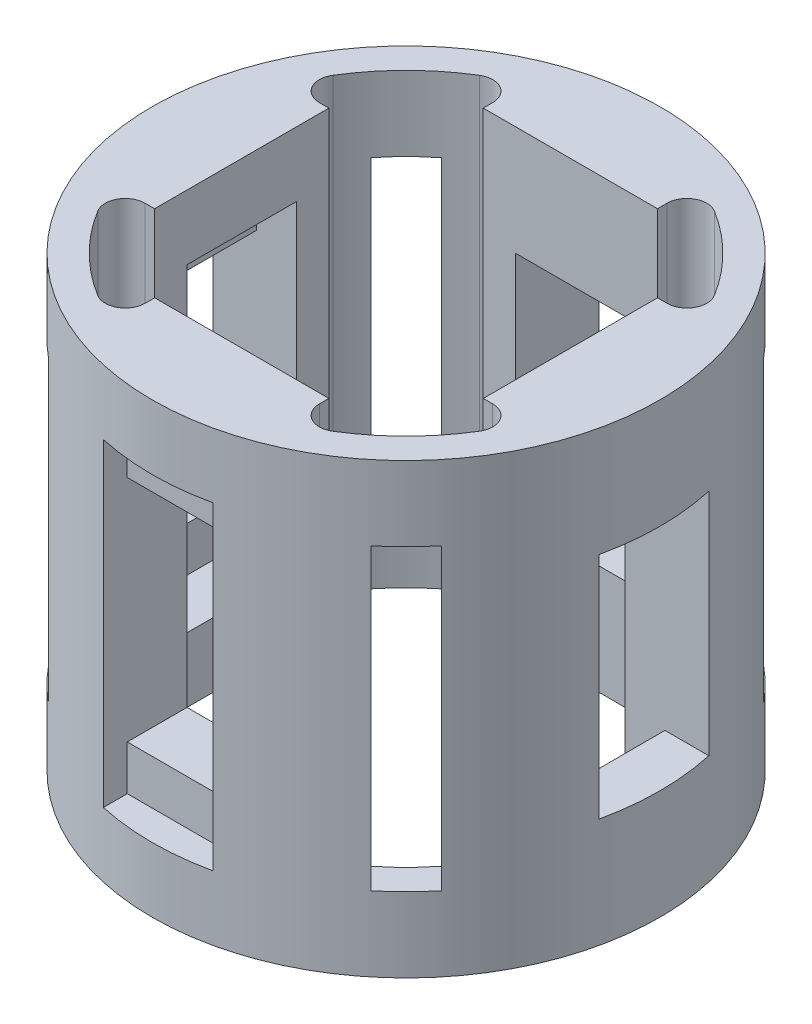
SolidWorks part; units mm, degrees
ref_plane "Front Plane" through (0, 0, 0) normal (0, 0, 1) x (1, 0, 0)
ref_plane "Top Plane" through (0, 0, 0) normal (0, 1, 0) x (1, 0, 0)
ref_plane "Right Plane" through (0, 0, 0) normal (1, 0, 0) x (0, 0, -1)
sketch "Sketch1" plane through (0, 0, 0) normal (0, 1, 0) x (1, 0, 0)
  line L5 (-8.75, -19.5) -> (8.75, -19.5)
  line L6 (-8.75, -19.5) -> (-8.75, -25.5)
  line L7 (-8.75, -25.5) -> (8.75, -25.5)
  line L8 (8.75, -19.5) -> (8.75, -25.5)
  line L9 (-8.75, -19.5) -> (8.75, -25.5) construction
  line L10 (-8.75, -25.5) -> (8.75, -19.5) construction
  line L11 (-25.5, 8.75) -> (-19.5, 8.75)
  line L12 (-25.5, 8.75) -> (-25.5, -8.75)
  line L13 (-25.5, -8.75) -> (-19.5, -8.75)
  line L14 (-19.5, 8.75) -> (-19.5, -8.75)
  line L15 (-25.5, 8.75) -> (-19.5, -8.75) construction
  line L16 (-25.5, -8.75) -> (-19.5, 8.75) construction
  line L17 (-8.75, 25.5) -> (8.75, 25.5)
  line L18 (-8.75, 25.5) -> (-8.75, 19.5)
  line L19 (-8.75, 19.5) -> (8.75, 19.5)
  line L20 (8.75, 25.5) -> (8.75, 19.5)
  line L21 (-8.75, 25.5) -> (8.75, 19.5) construction
  line L22 (-8.75, 19.5) -> (8.75, 25.5) construction
  line L23 (19.5, 8.75) -> (25.5, 8.75)
  line L24 (19.5, 8.75) -> (19.5, -8.75)
  line L25 (19.5, -8.75) -> (25.5, -8.75)
  line L26 (25.5, 8.75) -> (25.5, -8.75)
  line L27 (19.5, 8.75) -> (25.5, -8.75) construction
  line L28 (19.5, -8.75) -> (25.5, 8.75) construction
  line L29 (-8.75, -19.5) -> (8.75, -19.5)
  line L30 (-8.75, -19.5) -> (-8.75, -16.5)
  line L31 (-8.75, -16.5) -> (8.75, -16.5)
  line L32 (8.75, -19.5) -> (8.75, -16.5)
  line L33 (-19.5, 8.75) -> (-16.5, 8.75)
  line L34 (-19.5, 8.75) -> (-19.5, -8.75)
  line L35 (-19.5, -8.75) -> (-16.5, -8.75)
  line L36 (-16.5, 8.75) -> (-16.5, -8.75)
  line L37 (19.5, -8.75) -> (16.5, -8.75)
  line L38 (19.5, -8.75) -> (19.5, 8.75)
  line L39 (19.5, 8.75) -> (16.5, 8.75)
  line L40 (16.5, -8.75) -> (16.5, 8.75)
  line L41 (-8.75, 19.5) -> (8.75, 19.5)
  line L42 (-8.75, 19.5) -> (-8.75, 16.5)
  line L43 (-8.75, 16.5) -> (8.75, 16.5)
  line L44 (8.75, 19.5) -> (8.75, 16.5)
  circle A0 centre (0, 0) radius 25.5
  circle A1 centre (0, 0) radius 22.5
  point P4 (0, -22.5)
  point P9 (-22.5, 0)
  point P14 (0, 22.5)
  point P19 (22.5, 0)
  dimension "D1" = 51
  dimension "D2" = 45
  dimension "D3" = 6
  dimension "D4" = 17.5
  dimension "D5" = 6
  dimension "D6" = 17.5
  dimension "D7" = 6
  dimension "D8" = 6
  dimension "D9" = 17.5
  dimension "D10" = 17.5
  dimension "D11" = 3
  dimension "D12" = 3
  dimension "D13" = 3
  dimension "D14" = 3
extrude "Boss-Extrude1" add sketch "Sketch1" along normal blind 45 contours A1 L13 A0 L6 | A1 L11 A0 L13 | A1 L18 A0 L11 | A1 L20 A0 L18 | L20 A1 L18 L19 | L44 L19 L42 L43 | L36 L33 L14 L35 | L11 A1 L13 L14 | A1 L6 A0 L8 | L6 A1 L8 L5 | L5 L32 L31 L30 | A1 L8 A0 L25 | L40 L37 L24 L39 | L25 A1 L23 L24 | A1 L25 A0 L23 | A1 L23 A0 L20 region at (0, 0, 18) region at (0, 0, 20.7666) region at (0, 0, 23.4443) region at (-16.5332, 0, 16.5332) region at (16.5332, 0, 16.5332) region at (-20.7666, 0, 0) region at (-23.4443, 0, 0) region at (23.4443, 0, 0) region at (20.7666, 0, 0) region at (-18, 0, 0) region at (-16.5332, 0, -16.5332) region at (18, 0, 0) region at (0, 0, -20.7666) region at (0, 0, -23.4443) region at (16.5332, 0, -16.5332) region at (0, 0, -18)
fillet "Fillet1" radius 2 8 edges at (20.7289, 22.5, -8.75) (20.7289, 22.5, 8.75) (8.75, 22.5, 20.7289) (-8.75, 22.5, -20.7289) (8.75, 22.5, -20.7289) (-8.75, 22.5, 20.7289) (-20.7289, 22.5, 8.75) (-20.7289, 22.5, -8.75)
ref_plane "Plane1" through (0, 0, 0) normal (0.7071, 0, -0.7071) x (-0.7071, 0, -0.7071)
sketch "Sketch2" plane through (0, 0, 0) normal (0.7071, 0, -0.7071) x (-0.7071, 0, -0.7071)
  line L0 (0, 0) -> (0, 22.5)
  line L2 (2.5, 7.5) -> (-2.5, 7.5)
  line L3 (2.5, 7.5) -> (2.5, 37.5)
  line L4 (2.5, 37.5) -> (-2.5, 37.5)
  line L5 (-2.5, 7.5) -> (-2.5, 37.5)
  line L6 (2.5, 7.5) -> (-2.5, 37.5) construction
  line L7 (2.5, 37.5) -> (-2.5, 7.5) construction
  dimension "D1" = 22.5
  dimension "D2" = 30
  dimension "D3" = 5
extrude "Cut-Extrude1" cut sketch "Sketch2" against normal through all and the other way through all contours L5 L2 L3 L4 region at (-0.8839, 7.8041, -0.8839)
ref_plane "Plane2" through (0, 0, 0) normal (0.7071, 0, 0.7071) x (0.7071, 0, -0.7071)
sketch "Sketch3" plane through (0, 0, 0) normal (0.7071, 0, 0.7071) x (0.7071, 0, -0.7071)
  line L0 (0, 0) -> (0, 22.5)
  line L2 (2.5, 37.5) -> (-2.5, 37.5)
  line L3 (2.5, 37.5) -> (2.5, 7.5)
  line L4 (2.5, 7.5) -> (-2.5, 7.5)
  line L5 (-2.5, 37.5) -> (-2.5, 7.5)
  line L6 (2.5, 37.5) -> (-2.5, 7.5) construction
  line L7 (2.5, 7.5) -> (-2.5, 37.5) construction
  dimension "D1" = 22.5
  dimension "D2" = 5
  dimension "D3" = 30
extrude "Cut-Extrude2" cut sketch "Sketch3" against normal through all and the other way through all contours L2 L5 L4 L3 region at (1.5527, 22.5, -1.5527)
sketch "Sketch4" plane through (0, 0, 0) normal (0, 0, 1) x (1, 0, 0)
  line L0 (0, 0) -> (0, 22.5)
  line L2 (-5.5, 34) -> (5.5, 34)
  line L3 (-5.5, 34) -> (-5.5, 11)
  line L4 (-5.5, 11) -> (5.5, 11)
  line L5 (5.5, 34) -> (5.5, 11)
  line L6 (-5.5, 34) -> (5.5, 11) construction
  line L7 (-5.5, 11) -> (5.5, 34) construction
  dimension "D1" = 22.5
  dimension "D2" = 11
  dimension "D3" = 23
extrude "Cut-Extrude3" cut sketch "Sketch4" against normal through all and the other way through all contours L5 L2 L3 L4 region at (0, 33.745, 0)
sketch "Sketch5" plane through (0, 0, 0) normal (1, 0, 0) x (0, 0, -1)
  line L0 (0, 0) -> (0, 22.5)
  line L2 (5.5, 11) -> (-5.5, 11)
  line L3 (5.5, 11) -> (5.5, 34)
  line L4 (5.5, 34) -> (-5.5, 34)
  line L5 (-5.5, 11) -> (-5.5, 34)
  line L6 (5.5, 11) -> (-5.5, 34) construction
  line L7 (5.5, 34) -> (-5.5, 11) construction
  dimension "D1" = 22.5
  dimension "D2" = 23
  dimension "D3" = 11
extrude "Cut-Extrude4" cut sketch "Sketch5" against normal through all and the other way through all contours L5 L2 L3 L4 region at (0, 11.255, -2.75)
sketch "Sketch6" plane through (16.5, 0, 0) normal (-1, 0, 0) x (0, 0, 1)
  line L1 (-5.5, 34) -> (5.5, 34)
  line L2 (-5.5, 34) -> (-5.5, 38.5)
  line L3 (-5.5, 38.5) -> (5.5, 38.5)
  line L4 (5.5, 34) -> (5.5, 38.5)
  line L5 (-5.5, 11) -> (5.5, 11)
  line L6 (-5.5, 11) -> (-5.5, 6.5)
  line L7 (-5.5, 6.5) -> (5.5, 6.5)
  line L8 (5.5, 11) -> (5.5, 6.5)
  dimension "D1" = 4.5
  dimension "D2" = 4.5
  dimension "D3" = 11
  dimension "D4" = 11
sketch "Sketch7" plane through (-16.5, 0, 0) normal (1, 0, 0) x (0, 0, -1)
  line L1 (5.5, 34) -> (-5.5, 34)
  line L2 (5.5, 34) -> (5.5, 38.5)
  line L3 (5.5, 38.5) -> (-5.5, 38.5)
  line L4 (-5.5, 34) -> (-5.5, 38.5)
  line L5 (5.5, 11) -> (-5.5, 11)
  line L6 (5.5, 11) -> (5.5, 6.5)
  line L7 (5.5, 6.5) -> (-5.5, 6.5)
  line L8 (-5.5, 11) -> (-5.5, 6.5)
  dimension "D1" = 4.5
  dimension "D2" = 4.5
  dimension "D3" = 11
  dimension "D4" = 11
sketch "Sketch10" plane through (-16.5, 0, 0) normal (1, 0, 0) x (0, 0, -1)
  line L1 (-5.5, 11) -> (5.5, 11)
  line L2 (-5.5, 11) -> (-5.5, 6.5)
  line L3 (-5.5, 6.5) -> (5.5, 6.5)
  line L4 (5.5, 11) -> (5.5, 6.5)
  dimension "D1" = 4.5
  dimension "D2" = 11
extrude "Cut-Extrude11" cut sketch "Sketch10" against normal blind 5
extrude "Cut-Extrude12" cut sketch "Sketch6" against normal blind 4
extrude "Cut-Extrude13" cut sketch "Sketch7" against normal blind 4
ref_plane "Plane3" through (0, 0, 25.5) normal (0, 0, 1) x (1, 0, 0)
ref_plane "Plane4" through (0, 0, -25.5) normal (0, 0, 1) x (1, 0, 0)
sketch "Sketch11" plane through (0, 0, 25.5) normal (0, 0, 1) x (1, 0, 0)
  line L1 (-5.5, 11) -> (5.5, 11)
  line L2 (-5.5, 11) -> (-5.5, 6.5)
  line L3 (-5.5, 6.5) -> (5.5, 6.5)
  line L4 (5.5, 11) -> (5.5, 6.5)
  line L5 (-5.5, 34) -> (5.5, 34)
  line L6 (-5.5, 34) -> (-5.5, 38.5)
  line L7 (-5.5, 38.5) -> (5.5, 38.5)
  line L8 (5.5, 34) -> (5.5, 38.5)
  dimension "D1" = 11
  dimension "D2" = 11
  dimension "D3" = 4.5
  dimension "D4" = 4.5
extrude "Cut-Extrude14" cut sketch "Sketch11" against normal blind 3
sketch "Sketch13" plane through (0, 0, -25.5) normal (0, 0, 1) x (1, 0, 0)
  line L1 (-5.5, 34) -> (5.5, 34)
  line L2 (-5.5, 34) -> (-5.5, 38.5)
  line L3 (-5.5, 38.5) -> (5.5, 38.5)
  line L4 (5.5, 34) -> (5.5, 38.5)
  line L5 (-5.5, 11) -> (5.5, 11)
  line L6 (-5.5, 11) -> (-5.5, 6.5)
  line L7 (-5.5, 6.5) -> (5.5, 6.5)
  line L8 (5.5, 11) -> (5.5, 6.5)
  dimension "D1" = 11
  dimension "D2" = 11
  dimension "D3" = 4.5
  dimension "D4" = 4.5
extrude "Cut-Extrude17" cut sketch "Sketch13" against normal blind 3 and the other way blind 3 contours L2 L1 L4 L3 | L6 L5 L8 L7
